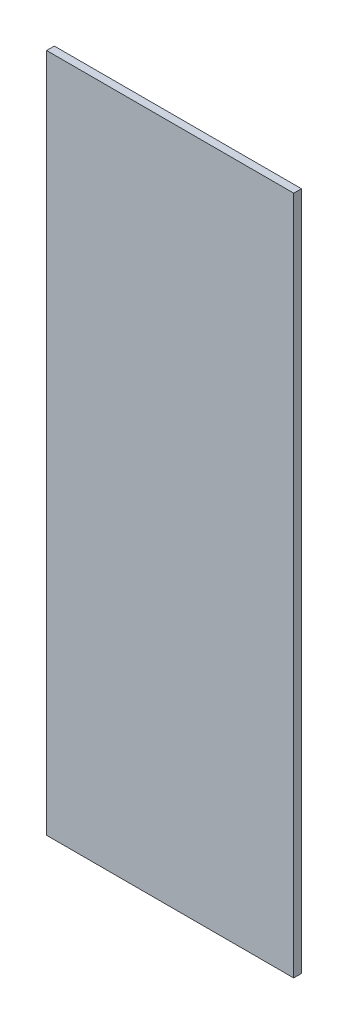
SolidWorks part; units mm, degrees
ref_plane "Front Plane" through (0, 0, 0) normal (0, 0, 1) x (1, 0, 0)
ref_plane "Top Plane" through (0, 0, 0) normal (0, 1, 0) x (1, 0, 0)
ref_plane "Right Plane" through (0, 0, 0) normal (1, 0, 0) x (0, 0, -1)
sketch "Sketch1" plane through (0, 0, 0) normal (0, 0, 1) x (1, 0, 0)
  line L1 (0, 0) -> (50.8, 0)
  line L2 (0, 0) -> (0, 139.7)
  line L3 (0, 139.7) -> (50.8, 139.7)
  line L4 (50.8, 0) -> (50.8, 139.7)
  dimension "D1" = 50.8
  dimension "D2" = 139.7
extrude "Boss-Extrude1" add sketch "Sketch1" along normal blind 1.5875
